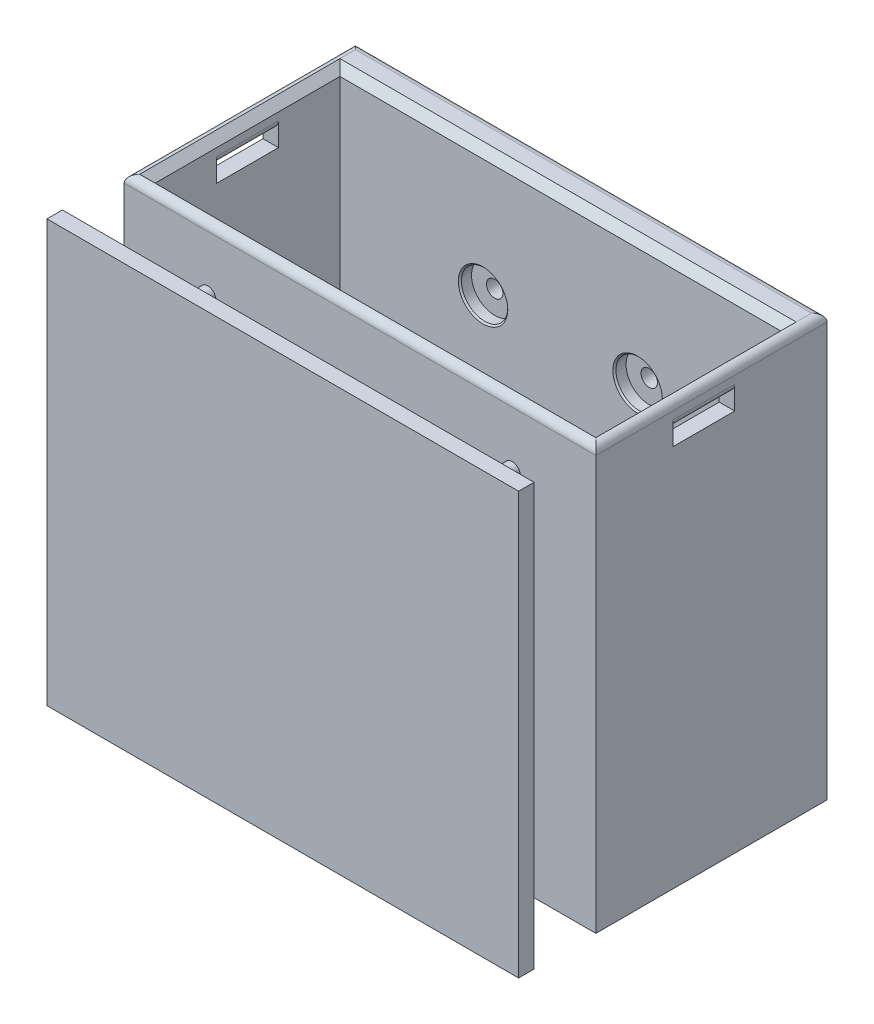
SolidWorks part; units mm, degrees
material "Hexcel AS4C (3000 Filaments)"
ref_plane "Front Plane" through (0, 0, 0) normal (0, 0, 1) x (1, 0, 0)
ref_plane "Top Plane" through (0, 0, 0) normal (0, 1, 0) x (1, 0, 0)
ref_plane "Right Plane" through (0, 0, 0) normal (1, 0, 0) x (0, 0, -1)
sketch "Sketch2" plane through (0, 0, 0) normal (0, 1, 0) x (1, 0, 0)
  line L1 (-90.551, -37.973) -> (90.551, -37.973)
  line L2 (-90.551, -37.973) -> (-90.551, 37.973)
  line L3 (-90.551, 37.973) -> (90.551, 37.973)
  line L4 (90.551, -37.973) -> (90.551, 37.973)
  line L5 (-90.551, -37.973) -> (90.551, 37.973) construction
  line L6 (-90.551, 37.973) -> (90.551, -37.973) construction
  line L7 (96.901, -44.323) -> (96.901, 50.673)
  line L8 (-96.901, -44.323) -> (96.901, -44.323)
  line L9 (-96.901, -44.323) -> (-96.901, 50.673)
  line L10 (-96.901, 44.323) -> (96.901, 44.323) construction
  line L11 (-96.901, 50.673) -> (96.901, 50.673)
  line L12 (-96.901, -44.323) -> (-96.901, 44.323) construction
  line L13 (96.901, -44.323) -> (96.901, 44.323) construction
  point P0 (0, 0)
  dimension "D1" = 6.35
  dimension "D2" = 181.102
  dimension "D3" = 75.946
  dimension "D4" = 12.7
extrude "Boss-Extrude1" add sketch "Sketch2" along normal blind 6.35 contours L1 L4 L3 L2 | L9 L8 L7 L4 L1 L2 L3 region at (0, 0, 0) region at (0, 0, 42.1647)
extrude "Boss-Extrude2" add sketch "Sketch2<3>" along normal blind 166.878 from surface starting at face at (0, 6.35, -3.175)
sketch "Sketch2<3>" plane through (0, 0, 0) normal (0, 1, 0) x (1, 0, 0) same geometry as "Sketch2"
sketch "Sketch3" plane through (0, 0, -37.973) normal (0, 0, 1) x (1, 0, 0)
  line L1 (-31.75, 58.039) -> (31.75, 58.039) construction
  line L2 (-31.75, 58.039) -> (-31.75, 121.539) construction
  line L3 (-31.75, 121.539) -> (31.75, 121.539) construction
  line L4 (-90.551, 6.35) -> (90.551, 6.35)
  line L5 (90.551, 6.35) -> (90.551, 173.228)
  line L6 (90.551, 173.228) -> (-90.551, 173.228)
  line L7 (-90.551, 173.228) -> (-90.551, 6.35)
  line L8 (-90.551, 6.35) -> (90.551, 6.35)
  line L9 (90.551, 6.35) -> (90.551, 173.228)
  line L10 (90.551, 173.228) -> (-90.551, 173.228)
  line L11 (-90.551, 173.228) -> (-90.551, 6.35)
  line L12 (31.75, 58.039) -> (31.75, 121.539) construction
  line L13 (-31.75, 58.039) -> (31.75, 121.539) construction
  line L14 (-31.75, 121.539) -> (31.75, 58.039) construction
  circle A0 centre (-31.75, 121.539) radius 3.175
  circle A1 centre (31.75, 121.539) radius 3.175
  circle A2 centre (31.75, 58.039) radius 3.175
  circle A3 centre (-31.75, 58.039) radius 3.175
  point P2 (0, 89.789)
  point P4 (31.75, 121.539)
  point P6 (-31.75, 58.039)
  point P7 (-31.75, 121.539)
  point P8 (31.75, 58.039)
  point P9 (-90.551, 89.789)
  point P12 (0, 6.35)
  point P23 (-90.551, 89.789)
  dimension "D3" = 6.35
  dimension "D2" = 63.5
  dimension "D1" = 0
sketch "Sketch9" plane through (0, 0, -37.973) normal (0, 0, 1) x (1, 0, 0)
  point P0 (-31.75, 121.539)
  point P2 (31.75, 121.539)
  point P5 (31.75, 58.039)
  point P8 (-31.75, 58.039)
hole_wizard "CBORE for 1/4 Hex Head Bolt2" positions "Sketch9" profile "Sketch8" counterbore size "1/4" standard "ANSI Inch" end condition through all
sketch "Sketch8" plane through (-31.75, 121.539, -37.973) normal (1, 0, 0) x (0, -1, 0)
  line L0 (0, 0) -> (0, 12.7)
  line L1 (0, 12.7) -> (3.3782, 12.7)
  line L3 (3.3782, 12.7) -> (3.3782, 4.7752)
  line L4 (9.525, 4.7752) -> (3.3782, 4.7752)
  line L5 (9.525, 4.7752) -> (9.525, 0.635)
  line L6 (9.525, 0.635) -> (10.16, 0)
  line L7 (10.16, 0) -> (0, 0)
  line L8 (-9.525, 0.635) -> (-10.16, 0) construction
  line L11 (0, -6.35) -> (0, 107.95) construction
  dimension "Thru Hole Dia." = 6.7564
  dimension "Thru Hole Depth" = 12.7
  dimension "C'Bore Dia." = 19.05
  dimension "C'Bore Depth" = 4.7752
  dimension "Near C'Sink Dia." = 20.32
  dimension "Near C'Sink Angle" = 90
sketch "Sketch10" plane through (0, 0, 44.323) normal (0, 0, 1) x (1, 0, 0)
  line L0 (-90.551, 173.228) -> (90.551, 6.35) construction
  line L1 (90.551, 173.228) -> (-90.551, 6.35) construction
  line L2 (90.551, 6.35) -> (62.5324, 32.168) construction
  line L3 (90.551, 173.228) -> (62.5324, 147.41) construction
  line L4 (-90.551, 6.35) -> (90.551, 6.35)
  line L5 (-90.551, 173.228) -> (-90.551, 6.35)
  line L6 (90.551, 173.228) -> (-90.551, 173.228)
  line L7 (90.551, 6.35) -> (90.551, 173.228)
  line L8 (-90.551, 6.35) -> (90.551, 6.35)
  line L9 (-90.551, 173.228) -> (-90.551, 6.35)
  line L10 (90.551, 173.228) -> (-90.551, 173.228)
  line L11 (90.551, 6.35) -> (90.551, 173.228)
  line L12 (-96.901, 0) -> (96.901, 0)
  line L13 (96.901, 0) -> (96.901, 173.228)
  line L14 (96.901, 173.228) -> (-96.901, 173.228)
  line L15 (-96.901, 173.228) -> (-96.901, 0)
  line L16 (-96.901, 0) -> (96.901, 0)
  line L17 (96.901, 0) -> (96.901, 173.228)
  line L18 (96.901, 173.228) -> (-96.901, 173.228)
  line L19 (-96.901, 173.228) -> (-96.901, 0)
  line L20 (-90.551, 173.228) -> (-62.5324, 147.41) construction
  line L21 (-90.551, 6.35) -> (-62.5324, 32.168) construction
  circle A0 centre (-62.5324, 147.41) radius 4.7625
  circle A1 centre (62.5324, 147.41) radius 4.7625
  circle A2 centre (62.5324, 32.168) radius 4.7625
  circle A3 centre (-62.5324, 32.168) radius 4.7625
  point P6 (62.5324, 147.41)
  point P8 (62.5324, 32.168)
  point P10 (-62.5324, 147.41)
  point P12 (-62.5324, 32.168)
  dimension "D3" = 9.525
  dimension "D4" = 38.1
sketch "Sketch12" plane through (0, 0, 44.323) normal (0, 0, 1) x (1, 0, 0)
  circle A0 centre (-62.5324, 32.168) radius 4.7625 construction
  circle A1 centre (62.5324, 32.168) radius 4.7625 construction
  circle A2 centre (62.5324, 147.41) radius 4.7625 construction
  circle A3 centre (-62.5324, 147.41) radius 4.7625 construction
  circle A4 centre (-62.5324, 32.168) radius 4.7625
  circle A5 centre (62.5324, 32.168) radius 4.7625
  circle A6 centre (62.5324, 147.41) radius 4.7625
  circle A7 centre (-62.5324, 147.41) radius 4.7625
  circle A8 centre (-62.5324, 147.41) radius 3.302
  circle A9 centre (62.5324, 147.41) radius 3.302
  circle A10 centre (62.5324, 32.168) radius 3.302
  circle A11 centre (-62.5324, 32.168) radius 3.302
  dimension "D1" = 6.604
extrude "Boss-Extrude3" add sketch "Sketch12" along normal blind 25.4 separate body contours A8 | A9 | A10 | A11 region at (-62.5324, 147.41, 44.323) region at (62.5324, 147.41, 44.323) region at (62.5324, 32.168, 44.323) region at (-62.5324, 32.168, 44.323)
sketch "Sketch13" plane through (0, 0, 44.323) normal (0, 0, 1) x (1, 0, 0)
  line L4 (-96.901, 0) -> (96.901, 0)
  line L5 (96.901, 0) -> (96.901, 173.228)
  line L6 (96.901, 173.228) -> (-96.901, 173.228)
  line L7 (-96.901, 173.228) -> (-96.901, 0)
  line L8 (-96.901, 0) -> (96.901, 0)
  line L9 (96.901, 0) -> (96.901, 173.228)
  line L10 (96.901, 173.228) -> (-96.901, 173.228)
  line L11 (-96.901, 173.228) -> (-96.901, 0)
  dimension "D1" = 0
extrude "Boss-Extrude4" add sketch "Sketch13" along normal blind 6.35 from surface separate body starting at face at (-59.2304, 147.41, 69.723)
sketch "Sketch16" plane through (96.901, 0, 0) normal (1, 0, 0) x (0, 0, -1)
  line L0 (0, 160.528) -> (0, 173.228) construction
  line L1 (-12.7, 157.353) -> (12.7, 157.353)
  line L2 (-12.7, 157.353) -> (-12.7, 163.703)
  line L3 (-12.7, 163.703) -> (12.7, 163.703)
  line L4 (-37.973, 6.35) -> (37.973, 6.35)
  line L5 (-37.973, 173.228) -> (-37.973, 6.35)
  line L6 (37.973, 173.228) -> (-37.973, 173.228)
  line L7 (37.973, 6.35) -> (37.973, 173.228)
  line L8 (-37.973, 6.35) -> (37.973, 6.35)
  line L9 (-37.973, 173.228) -> (-37.973, 6.35)
  line L10 (37.973, 173.228) -> (-37.973, 173.228)
  line L11 (37.973, 6.35) -> (37.973, 173.228)
  line L12 (12.7, 157.353) -> (12.7, 163.703)
  line L13 (-12.7, 157.353) -> (12.7, 163.703) construction
  line L14 (-12.7, 163.703) -> (12.7, 157.353) construction
  point P2 (0, 160.528)
  point P10 (0, 173.228)
  dimension "D2" = 12.7
  dimension "D3" = 25.4
  dimension "D4" = 6.35
  dimension "D1" = 0
extrude "Cut-Extrude2" cut sketch "Sketch16" against normal through all contours L1 L12 L3 L2 region at (96.901, 160.528, 0)
fillet "Fillet1" radius 3.175 4 edges at (90.551, 163.703, 0) (96.901, 163.703, 0) (-90.551, 163.703, 0) (-96.901, 163.703, 0)
fillet "Fillet2" radius 3.175 4 edges at (-96.901, 173.228, -3.175) (0, 173.228, 44.323) (96.901, 173.228, -3.175) (0, 173.228, -50.673)
chamfer "Chamfer1" distance 3.175 4 edges at (90.551, 173.228, 0) (0, 173.228, 37.973) (-90.551, 173.228, 0) (0, 173.228, -37.973)
equation "\"wall_thick\"= 0.25in"
equation "\"D1@Boss-Extrude1\"=\"wall_thick\""
equation "\"D1@Sketch2\"=\"wall_thick\""
equation "\"bolt_dia\"= 0.25in"
equation "\"D3@Sketch10\"=\"bolt_dia\"+0.125in"
